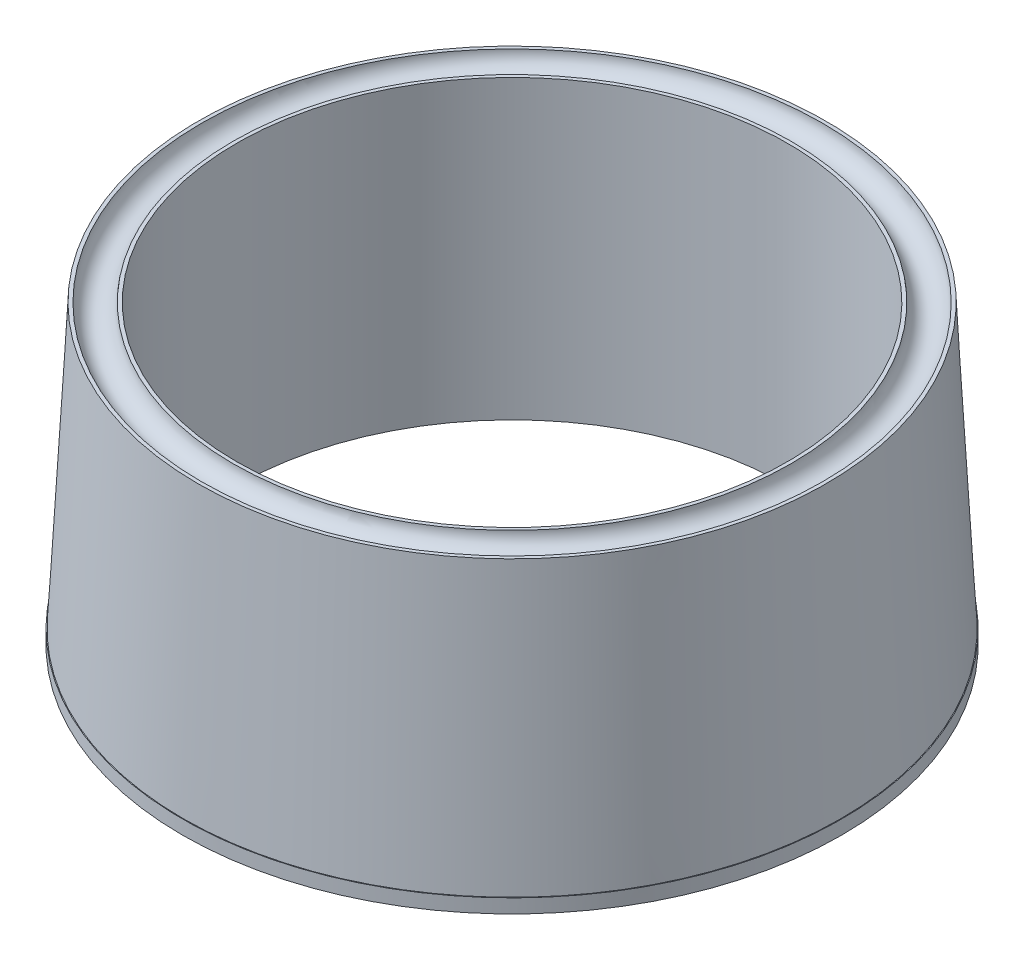
SolidWorks part; units mm, degrees
ref_plane "Płaszczyzna przednia" through (0, 0, 0) normal (0, 0, 1) x (1, 0, 0)
ref_plane "Płaszczyzna górna" through (0, 0, 0) normal (0, 1, 0) x (1, 0, 0)
ref_plane "Płaszczyzna prawa" through (0, 0, 0) normal (1, 0, 0) x (0, 0, -1)
sketch "Sketch1" plane through (0, 0, 0) normal (0, 1, 0) x (1, 0, 0)
  circle A0 centre (0, 0) radius 45
extrude "Boss-Extrude1" add sketch "Sketch1" along normal blind 42.5
sketch "Sketch2" plane through (0, 42.5, 0) normal (0, 1, 0) x (1, 0, 0)
  circle A0 centre (0, 0) radius 39.5
extrude "Cut-Extrude1" cut sketch "Sketch2" against normal blind 148
draft "Draft2" type of draft neutral plane draft angle 3 faces to draft 1 face at (0, 42.5, 45) neutral plane through (0, 42.5, 0) neutral plane normal (0, 1, 0) parameters "D1"=3
sketch "Sketch5" plane through (0, 0, 0) normal (0, -1, 0) x (1, 0, 0)
  line L0 (-39.5, 0) -> (-47.2273, 0)
  circle A0 centre (0, 0) radius 39.5 construction
  circle A1 centre (0, 0) radius 47.2273 construction
  dimension "D1" = 7.7273
sketch "Sketch6" plane through (0, 0, 0) normal (0, -1, 0) x (1, 0, 0)
  line L0 (-39.5, 0) -> (-47.2273, 0) construction
  line L1 (-43.3637, 0) -> (-21.6818, -37.554)
  line L2 (-21.6818, -37.554) -> (21.6818, -37.554)
  line L3 (21.6818, -37.554) -> (43.3637, 0)
  line L4 (43.3637, 0) -> (21.6818, 37.554)
  line L5 (21.6818, 37.554) -> (-21.6818, 37.554)
  line L6 (-21.6818, 37.554) -> (-43.3637, 0)
  line L7 (-21.6818, 34.3209) -> (-18.8818, 35.9375)
  line L8 (-18.8818, 35.9375) -> (-18.8818, 39.1706)
  line L9 (-18.8818, 39.1706) -> (-21.6818, 40.7872)
  line L10 (-21.6818, 40.7872) -> (-24.4818, 39.1706)
  line L11 (-24.4818, 39.1706) -> (-24.4818, 35.9375)
  line L12 (-24.4818, 35.9375) -> (-21.6818, 34.3209)
  line L13 (21.6818, 34.3209) -> (24.4818, 35.9375)
  line L14 (24.4818, 35.9375) -> (24.4818, 39.1706)
  line L15 (24.4818, 39.1706) -> (21.6818, 40.7872)
  line L16 (21.6818, 40.7872) -> (18.8818, 39.1706)
  line L17 (18.8818, 39.1706) -> (18.8818, 35.9375)
  line L18 (18.8818, 35.9375) -> (21.6818, 34.3209)
  line L19 (43.3637, -3.2332) -> (46.1637, -1.6166)
  line L20 (46.1637, -1.6166) -> (46.1637, 1.6166)
  line L21 (46.1637, 1.6166) -> (43.3637, 3.2332)
  line L22 (43.3637, 3.2332) -> (40.5637, 1.6166)
  line L23 (40.5637, 1.6166) -> (40.5637, -1.6166)
  line L24 (40.5637, -1.6166) -> (43.3637, -3.2332)
  line L25 (-43.3637, -3.2332) -> (-40.5637, -1.6166)
  line L26 (-40.5637, -1.6166) -> (-40.5637, 1.6166)
  line L27 (-40.5637, 1.6166) -> (-43.3637, 3.2332)
  line L28 (-43.3637, 3.2332) -> (-46.1637, 1.6166)
  line L29 (-46.1637, 1.6166) -> (-46.1637, -1.6166)
  line L30 (-46.1637, -1.6166) -> (-43.3637, -3.2332)
  line L31 (-21.6818, -34.3209) -> (-24.4818, -35.9375)
  line L32 (-24.4818, -35.9375) -> (-24.4818, -39.1706)
  line L33 (-24.4818, -39.1706) -> (-21.6818, -40.7872)
  line L34 (-21.6818, -40.7872) -> (-18.8818, -39.1706)
  line L35 (-18.8818, -39.1706) -> (-18.8818, -35.9375)
  line L36 (-18.8818, -35.9375) -> (-21.6818, -34.3209)
  line L37 (21.6818, -40.7872) -> (24.4818, -39.1706)
  line L38 (24.4818, -39.1706) -> (24.4818, -35.9375)
  line L39 (24.4818, -35.9375) -> (21.6818, -34.3209)
  line L40 (21.6818, -34.3209) -> (18.8818, -35.9375)
  line L41 (18.8818, -35.9375) -> (18.8818, -39.1706)
  line L42 (18.8818, -39.1706) -> (21.6818, -40.7872)
  circle A0 centre (0, 0) radius 37.554 construction
  circle A1 centre (-21.6818, 37.554) radius 2.8 construction
  circle A2 centre (21.6818, 37.554) radius 2.8 construction
  circle A3 centre (43.3637, 0) radius 2.8 construction
  circle A4 centre (-43.3637, 0) radius 2.8 construction
  circle A5 centre (-21.6818, -37.554) radius 2.8 construction
  circle A6 centre (21.6818, -37.554) radius 2.8 construction
  dimension "D1" = 2.8
  dimension "D2" = 1.0637
  dimension "D3" = 2.8
  dimension "D4" = 2.8
  dimension "D5" = 2.8
  dimension "D6" = 2.8
  dimension "D7" = 2.8
  dimension "D8" = 2.8
extrude "Cut-Extrude2" cut sketch "Sketch6" against normal blind 5 contours L11 L12 L6 L5 L8 L9 L10 | L16 L17 L5 L4 L13 L14 L15 | L3 L24 L19 L20 L21 L22 L4 | L41 L42 L37 L38 L39 L3 L2 | L34 L35 L2 L1 L31 L32 L33 | L29 L30 L25 L1 L6 L27 L28 | L26 L27 L6 L1 L25 | L6 L12 L7 L8 L5 | L17 L18 L13 L4 L5 | L23 L24 L3 L4 L22 | L40 L41 L2 L3 L39 | L35 L36 L31 L1 L2 region at (-41.7303, 0, 0) region at (-44.1803, 0, 0) region at (-20.8652, 0, -36.1395) region at (-22.0902, 0, -38.2613) region at (-22.0902, 0, 38.2613) region at (-20.8652, 0, 36.1395) region at (20.8652, 0, -36.1395) region at (22.0902, 0, -38.2613) region at (22.0902, 0, 38.2613) region at (20.8652, 0, 36.1395) region at (41.7303, 0, 0) region at (44.1803, 0, 0)
sketch "Sketch7" plane through (0, 0, 0) normal (0, -1, 0) x (1, 0, 0)
  circle A0 centre (0, 0) radius 47.2273
extrude "Boss-Extrude2" add sketch "Sketch7" against normal blind 2
sketch "Sketch8" plane through (0, 2, 0) normal (0, 1, 0) x (1, 0, 0)
  circle A0 centre (0, 0) radius 39.5
extrude "Cut-Extrude3" cut sketch "Sketch8" against normal blind 66
sketch "Sketch9" plane through (0, 0, 0) normal (0, -1, 0) x (1, 0, 0)
  line L1 (-43.2851, 0) -> (-21.6425, -37.486)
  line L2 (-21.6425, -37.486) -> (21.6425, -37.486)
  line L3 (21.6425, -37.486) -> (43.2851, 0)
  line L4 (43.2851, 0) -> (21.6425, 37.486)
  line L5 (21.6425, 37.486) -> (-21.6425, 37.486)
  line L6 (-21.6425, 37.486) -> (-43.2851, 0)
  circle A0 centre (0, 0) radius 37.486 construction
  circle A1 centre (-43.2851, 0) radius 1.6
  circle A2 centre (-21.6425, 37.486) radius 1.6
  circle A3 centre (21.6425, 37.486) radius 1.6
  circle A4 centre (43.2851, 0) radius 1.6
  circle A5 centre (21.6425, -37.486) radius 1.6
  circle A6 centre (-21.6425, -37.486) radius 1.6
extrude "Cut-Extrude4" cut sketch "Sketch9" against normal blind 15 contours L6 A1 L1 | L1 A1 L6 | L5 A2 L6 | L5 A3 L4 | L4 A3 L5 | L4 A4 L3 | L3 A4 L4 | L2 A5 L3 | L3 A5 L2 | L1 A6 L2 | L2 A6 L1 | A2 region at (-42.4029, 0, 0) region at (-43.7261, 0, 0) region at (-21.2015, 0, -36.722) region at (-21.8631, 0, -37.8679) region at (-21.8631, 0, 37.8679) region at (21.2015, 0, -36.722) region at (21.8631, 0, -37.8679) region at (21.8631, 0, 37.8679) region at (21.2015, 0, 36.722) region at (42.4029, 0, 0) region at (43.7261, 0, 0)
sketch "Sketch10" plane through (0, 42.5, 0) normal (0, 1, 0) x (1, 0, 0)
  circle A2 centre (0, 0) radius 42.25
sweep "Cut-Sweep1" cut path "Sketch10" circular profile diameter 4.5 parameters "D3"=4.5
